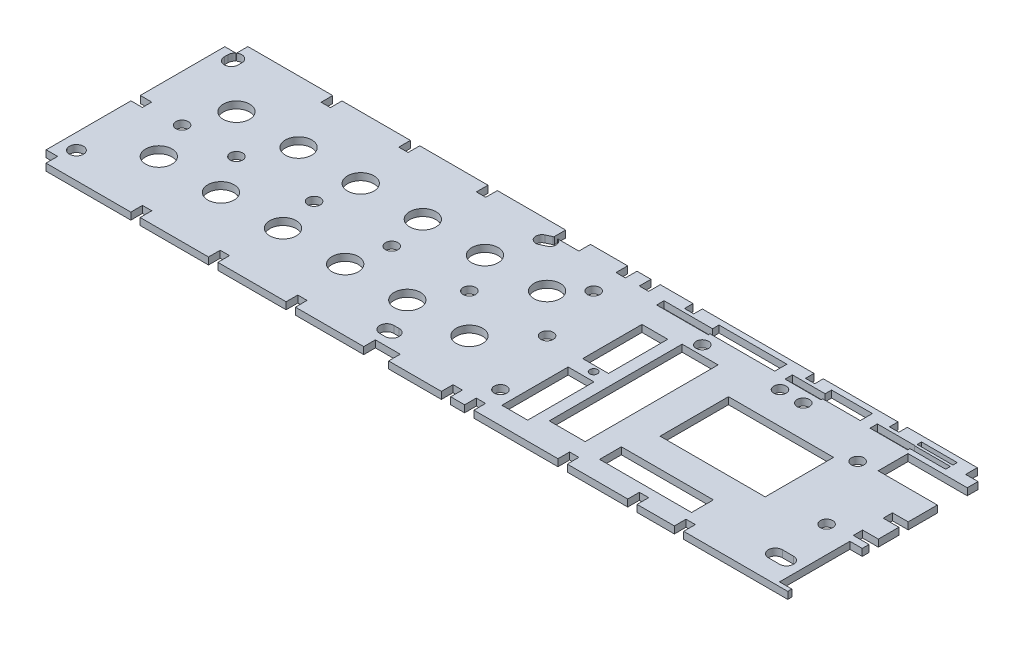
SolidWorks part; units mm, degrees
ref_plane "Front Plane" through (0, 0, 0) normal (0, 0, 1) x (1, 0, 0)
ref_plane "Top Plane" through (0, 0, 0) normal (0, 1, 0) x (1, 0, 0)
ref_plane "Right Plane" through (0, 0, 0) normal (1, 0, 0) x (0, 0, -1)
sketch "Sketch1" plane through (0, 0, 0) normal (0, 1, 0) x (1, 0, 0)
  line L0 (485, 0) -> (485, 130) construction
  line L1 (0, 130) -> (485, 130)
  line L2 (0, 130) -> (0, 0)
  line L3 (0, 0) -> (485, 0)
  line L4 (485, 130) -> (485, 0)
  line L5 (0, 130) -> (0, 0) construction
  line L6 (485, 130) -> (0, 130) construction
  line L7 (0, 0) -> (485, 0) construction
  line L8 (444.7316, 118.9355) -> (444.7316, 117.5)
  line L9 (485, 47.9413) -> (477.0415, 47.9413)
  line L10 (485, 47.9413) -> (485, 2.6445)
  line L11 (485, 2.6445) -> (477.0415, 2.6445)
  line L12 (477.0415, 47.9413) -> (477.0415, 2.6445)
  line L13 (485, 77.533) -> (474.8926, 77.533)
  line L14 (485, 77.533) -> (485, 71.533)
  line L15 (485, 71.533) -> (474.8926, 71.533)
  line L16 (474.8926, 77.533) -> (474.8926, 71.533)
  line L17 (485, 58.3069) -> (474.8926, 58.3069)
  line L18 (485, 58.3069) -> (485, 52.3069)
  line L19 (485, 52.3069) -> (474.8926, 52.3069)
  line L20 (474.8926, 58.3069) -> (474.8926, 52.3069)
  line L21 (485, 115.574) -> (446.8521, 115.574)
  line L22 (485, 115.574) -> (485, 96.3378)
  line L23 (485, 96.3378) -> (446.8521, 96.3378)
  line L24 (446.8521, 115.574) -> (446.8521, 96.3378)
  line L25 (444.7316, 126.4) -> (467.7258, 126.4)
  line L26 (444.7316, 126.4) -> (444.7316, 123.5923)
  line L27 (444.7316, 123.5923) -> (467.7258, 123.5923)
  line L28 (467.7258, 126.4) -> (467.7258, 123.5923)
  line L29 (467.6918, 122.0219) -> (444.7316, 122.0219)
  line L30 (467.6918, 122.0219) -> (467.6918, 118.9355)
  line L31 (467.6918, 118.9355) -> (444.7316, 118.9355)
  line L33 (425.9983, 130) -> (431.9983, 130)
  line L34 (425.9983, 130) -> (425.9983, 124.5)
  line L35 (425.9983, 124.5) -> (431.9983, 124.5)
  line L36 (431.9983, 130) -> (431.9983, 124.5)
  line L37 (420.448, 122.2354) -> (444.7316, 122.2354)
  line L38 (420.448, 122.2354) -> (420.448, 117.5)
  line L39 (420.448, 117.5) -> (444.7316, 117.5)
  line L40 (444.7316, 122.2354) -> (444.7316, 122.0219)
  line L41 (10, 119.0046) -> (10, 116.6922) construction
  line L42 (371.8879, 130) -> (377.8879, 130)
  line L43 (371.8879, 130) -> (371.8879, 124.5)
  line L44 (371.8879, 124.5) -> (377.8879, 124.5)
  line L45 (377.8879, 130) -> (377.8879, 124.5)
  line L46 (294.0008, 130) -> (300.0008, 130)
  line L47 (294.0008, 130) -> (294.0008, 124.5)
  line L48 (294.0008, 124.5) -> (300.0008, 124.5)
  line L49 (300.0008, 130) -> (300.0008, 124.5)
  line L50 (266.9165, 130) -> (272.9165, 130)
  line L51 (266.9165, 130) -> (266.9165, 122.5)
  line L52 (266.9165, 122.5) -> (272.9165, 122.5)
  line L53 (272.9165, 130) -> (272.9165, 122.5)
  line L54 (251.9112, 130) -> (257.9112, 130)
  line L55 (251.9112, 130) -> (251.9112, 122.5)
  line L56 (251.9112, 122.5) -> (257.9112, 122.5)
  line L57 (257.9112, 130) -> (257.9112, 122.5)
  line L58 (211.9807, 130) -> (227.9807, 130)
  line L59 (211.9807, 130) -> (211.9807, 122.5)
  line L60 (211.9807, 122.5) -> (227.9807, 122.5)
  line L61 (227.9807, 130) -> (227.9807, 122.5)
  line L62 (161.992, 130) -> (167.992, 130)
  line L63 (161.992, 130) -> (161.992, 122.5)
  line L64 (161.992, 122.5) -> (167.992, 122.5)
  line L65 (167.992, 130) -> (167.992, 122.5)
  line L66 (112.0325, 130) -> (118.0325, 130)
  line L67 (112.0325, 130) -> (112.0325, 122.5)
  line L68 (112.0325, 122.5) -> (118.0325, 122.5)
  line L69 (118.0325, 130) -> (118.0325, 122.5)
  line L70 (62.0027, 130) -> (68.0027, 130)
  line L71 (62.0027, 130) -> (62.0027, 122.5)
  line L72 (62.0027, 122.5) -> (68.0027, 122.5)
  line L73 (68.0027, 130) -> (68.0027, 122.5)
  line L74 (425.0315, 89.4923) -> (357.3425, 89.4923)
  line L75 (425.0315, 89.4923) -> (425.0315, 45.4306)
  line L76 (425.0315, 45.4306) -> (357.3425, 45.4306)
  line L77 (357.3425, 89.4923) -> (357.3425, 45.4306)
  line L78 (410.025, 27.0715) -> (350.7971, 27.0715)
  line L79 (410.025, 27.0715) -> (410.025, 13.0229)
  line L80 (410.025, 13.0229) -> (350.7971, 13.0229)
  line L81 (350.7971, 27.0715) -> (350.7971, 13.0229)
  line L82 (289.1745, 101.9445) -> (305.7775, 101.9445)
  line L83 (289.1745, 101.9445) -> (289.1745, 63.8011)
  line L84 (289.1745, 11.7457) -> (305.7775, 11.7457)
  line L85 (305.7775, 101.9445) -> (305.7775, 63.8011)
  line L86 (313.1211, 103.8603) -> (336.2695, 103.8603)
  line L87 (313.1211, 103.8603) -> (313.1211, 18.2911)
  line L88 (313.1211, 18.2911) -> (336.2695, 18.2911)
  line L89 (336.2695, 103.8603) -> (336.2695, 18.2911)
  line L90 (411.997, 0) -> (417.997, 0)
  line L91 (411.997, 0) -> (411.997, 7.5)
  line L92 (411.997, 7.5) -> (417.997, 7.5)
  line L93 (417.997, 0) -> (417.997, 7.5)
  line L94 (381.9632, 0) -> (387.9632, 0)
  line L95 (381.9632, 0) -> (381.9632, 7.5)
  line L96 (381.9632, 7.5) -> (387.9632, 7.5)
  line L97 (387.9632, 0) -> (387.9632, 7.5)
  line L98 (337.0209, 0) -> (343.0209, 0)
  line L99 (337.0209, 0) -> (337.0209, 7.5)
  line L100 (337.0209, 7.5) -> (343.0209, 7.5)
  line L101 (343.0209, 0) -> (343.0209, 7.5)
  line L102 (261.9696, 0) -> (267.9696, 0)
  line L103 (261.9696, 0) -> (261.9696, 7.5)
  line L104 (261.9696, 7.5) -> (267.9696, 7.5)
  line L105 (267.9696, 0) -> (267.9696, 7.5)
  line L106 (276.9208, 0) -> (282.9208, 0)
  line L107 (276.9208, 0) -> (276.9208, 7.5)
  line L108 (276.9208, 7.5) -> (282.9208, 7.5)
  line L109 (282.9208, 0) -> (282.9208, 7.5)
  line L110 (211.9807, 0) -> (227.9807, 0)
  line L111 (211.9807, 0) -> (211.9807, 7.5)
  line L112 (211.9807, 7.5) -> (227.9807, 7.5)
  line L113 (227.9807, 0) -> (227.9807, 7.5)
  line L114 (161.992, 0) -> (167.992, 0)
  line L115 (161.992, 0) -> (161.992, 7.5)
  line L116 (161.992, 7.5) -> (167.992, 7.5)
  line L117 (167.992, 0) -> (167.992, 7.5)
  line L118 (112.0325, 0) -> (118.0325, 0)
  line L119 (112.0325, 0) -> (112.0325, 7.5)
  line L120 (112.0325, 7.5) -> (118.0325, 7.5)
  line L121 (118.0325, 0) -> (118.0325, 7.5)
  line L122 (62.0027, 0) -> (68.0027, 0)
  line L123 (62.0027, 0) -> (62.0027, 7.5)
  line L124 (62.0027, 7.5) -> (68.0027, 7.5)
  line L125 (68.0027, 0) -> (68.0027, 7.5)
  line L126 (0, 130) -> (7.3855, 130)
  line L127 (0, 130) -> (0, 122.5)
  line L128 (0, 122.5) -> (7.3855, 122.5)
  line L129 (7.3855, 130) -> (7.3855, 122.5)
  line L130 (0, 0) -> (7.3855, 0)
  line L131 (0, 0) -> (0, 7.5)
  line L132 (0, 7.5) -> (7.3855, 7.5)
  line L133 (7.3855, 0) -> (7.3855, 7.5)
  line L134 (485, 130) -> (477.0415, 130)
  line L135 (485, 130) -> (485, 122.492)
  line L136 (485, 122.492) -> (477.0415, 122.492)
  line L137 (477.0415, 130) -> (477.0415, 122.492)
  line L138 (0, 68.0866) -> (7.3855, 68.0866)
  line L139 (0, 68.0866) -> (0, 62.0866)
  line L140 (0, 62.0866) -> (7.3855, 62.0866)
  line L141 (7.3855, 68.0866) -> (7.3855, 62.0866)
  line L142 (14.5, 119.0046) -> (14.5, 116.6922)
  line L143 (5.5, 119.0046) -> (5.5, 116.6922)
  line L144 (209.8069, 17) -> (213.2636, 17) construction
  line L145 (209.8069, 21.5) -> (213.2636, 21.5)
  line L146 (209.8069, 12.5) -> (213.2636, 12.5)
  line L147 (213.2636, 118.6281) -> (209.7734, 116.9719) construction
  line L148 (214.9785, 115.0144) -> (211.4883, 113.3581)
  line L149 (211.5487, 122.2419) -> (208.0585, 120.5856)
  line L150 (460, 17) -> (467.2539, 17) construction
  line L151 (460, 21.5) -> (467.2539, 21.5)
  line L152 (460, 12.5) -> (467.2539, 12.5)
  line L153 (289.1745, 54.4287) -> (289.1745, 11.7457)
  line L154 (283.0858, 122.2354) -> (314.3348, 122.2354)
  line L155 (283.0858, 122.2354) -> (283.0858, 117.5)
  line L156 (283.0858, 117.5) -> (316.3348, 117.5)
  line L157 (316.3348, 118.5927) -> (316.3348, 117.5)
  line L158 (365.7301, 122.2354) -> (386.8323, 122.2354)
  line L159 (365.7301, 122.2354) -> (365.7301, 117.5)
  line L160 (365.7301, 117.5) -> (388.8323, 117.5)
  line L161 (388.8323, 118.5927) -> (388.8323, 117.5)
  line L162 (358.0245, 126.4) -> (314.3348, 126.4)
  line L163 (358.0245, 126.4) -> (358.0245, 118.5927)
  line L164 (358.0245, 118.5927) -> (316.3348, 118.5927)
  line L165 (314.3348, 126.4) -> (314.3348, 122.2354)
  line L166 (413.0962, 126.4) -> (386.8323, 126.4)
  line L167 (413.0962, 126.4) -> (413.0962, 118.5927)
  line L168 (413.0962, 118.5927) -> (388.8323, 118.5927)
  line L169 (386.8323, 126.4) -> (386.8323, 122.2354)
  line L170 (305.7775, 63.8011) -> (289.1745, 63.8011)
  line L172 (305.7775, 54.4287) -> (289.1745, 54.4287)
  line L174 (305.7775, 54.4287) -> (305.7775, 11.7457)
  circle A0 centre (40.0138, 90.005) radius 8.5
  circle A1 centre (65, 65) radius 4
  circle A2 centre (80.0138, 90.005) radius 8.5
  circle A3 centre (120.0138, 90.005) radius 8.5
  circle A4 centre (160.0138, 90.005) radius 8.5
  circle A5 centre (200.0138, 90.005) radius 8.5
  circle A6 centre (240.0138, 90.005) radius 8.5
  circle A7 centre (80.0138, 40.005) radius 8.5
  circle A8 centre (120.0138, 40.005) radius 8.5
  circle A9 centre (160.0138, 40.005) radius 8.5
  circle A10 centre (200.0138, 40.005) radius 8.5
  circle A11 centre (240.0138, 40.005) radius 8.5
  circle A12 centre (40.0138, 40.005) radius 8.5
  circle A13 centre (30, 65) radius 4
  circle A14 centre (115, 65) radius 4
  circle A15 centre (165, 65) radius 4
  circle A16 centre (215, 65) radius 4
  circle A17 centre (265, 65) radius 4
  circle A18 centre (255, 105) radius 4
  circle A19 centre (280, 20) radius 4
  circle A20 centre (320, 110) radius 4
  circle A21 centre (460, 50) radius 4
  circle A22 centre (435, 95) radius 4
  circle A23 centre (370, 110) radius 4
  circle A24 centre (385, 110) radius 4
  arc A25 (14.5, 119.0046) -> (5.5, 119.0046) centre (10, 119.0046) ccw
  arc A26 (5.5, 116.6922) -> (14.5, 116.6922) centre (10, 116.6922) ccw
  circle A27 centre (10, 17) radius 4.5
  arc A28 (209.8069, 21.5) -> (209.8069, 12.5) centre (209.8069, 17) ccw
  arc A29 (213.2636, 12.5) -> (213.2636, 21.5) centre (213.2636, 17) ccw
  arc A30 (214.9785, 115.0144) -> (211.5487, 122.2419) centre (213.2636, 118.6281) ccw
  arc A31 (208.0585, 120.5856) -> (211.4883, 113.3581) centre (209.7734, 116.9719) ccw
  arc A32 (460, 21.5) -> (460, 12.5) centre (460, 17) ccw
  arc A33 (467.2539, 12.5) -> (467.2539, 21.5) centre (467.2539, 17) ccw
  circle A34 centre (300, 60) radius 2.467
  point P202 (10, 117.8484)
  point P207 (211.5352, 17)
  point P216 (211.5185, 117.8)
  point P223 (463.6269, 17)
  dimension "D23" = 17
  dimension "D24" = 8
  dimension "D33" = 9
  dimension "D1" = 6
  dimension "D2" = 6
  dimension "D3" = 6
  dimension "D4" = 6
  dimension "D5" = 6
  dimension "D6" = 16
  dimension "D7" = 6
  dimension "D8" = 6
  dimension "D9" = 6
  dimension "D10" = 7.5
  dimension "D11" = 5.5
  dimension "D12" = 6
  dimension "D13" = 6
  dimension "D14" = 6
  dimension "D15" = 6
  dimension "D16" = 6
  dimension "D17" = 6
  dimension "D18" = 6
  dimension "D19" = 7.5
  dimension "D22" = 6
  dimension "D26" = 12.5
  dimension "D27" = 3.6
  dimension "D28" = 74.9387
  dimension "D29" = 47.3661
  dimension "D30" = 47.2438
  dimension "D31" = 10
  dimension "D32" = 10
  dimension "D34" = 9
  dimension "D35" = 17
  dimension "D36" = 9
  dimension "D37" = 12.2
  dimension "D38" = 8
  dimension "D39" = 17
  dimension "D40" = 9
  dimension "D20" = 6
  dimension "D21" = 2
  dimension "D25" = 5
extrude "Boss-Extrude1" add sketch "Sketch1" against normal blind 4.5 contours L138 L141 L140 L2 L132 L133 L3 L123 L124 L125 L119 L120 L121 L115 L116 L117 L111 L112 L113 L103 L104 L105 L107 L108 L109 L99 L100 L101 L95 L96 L97 L91 L92 L93 L4 L11 L12 L9 L19 L20 L17 region at (223.9114, 0, -64.3905)
